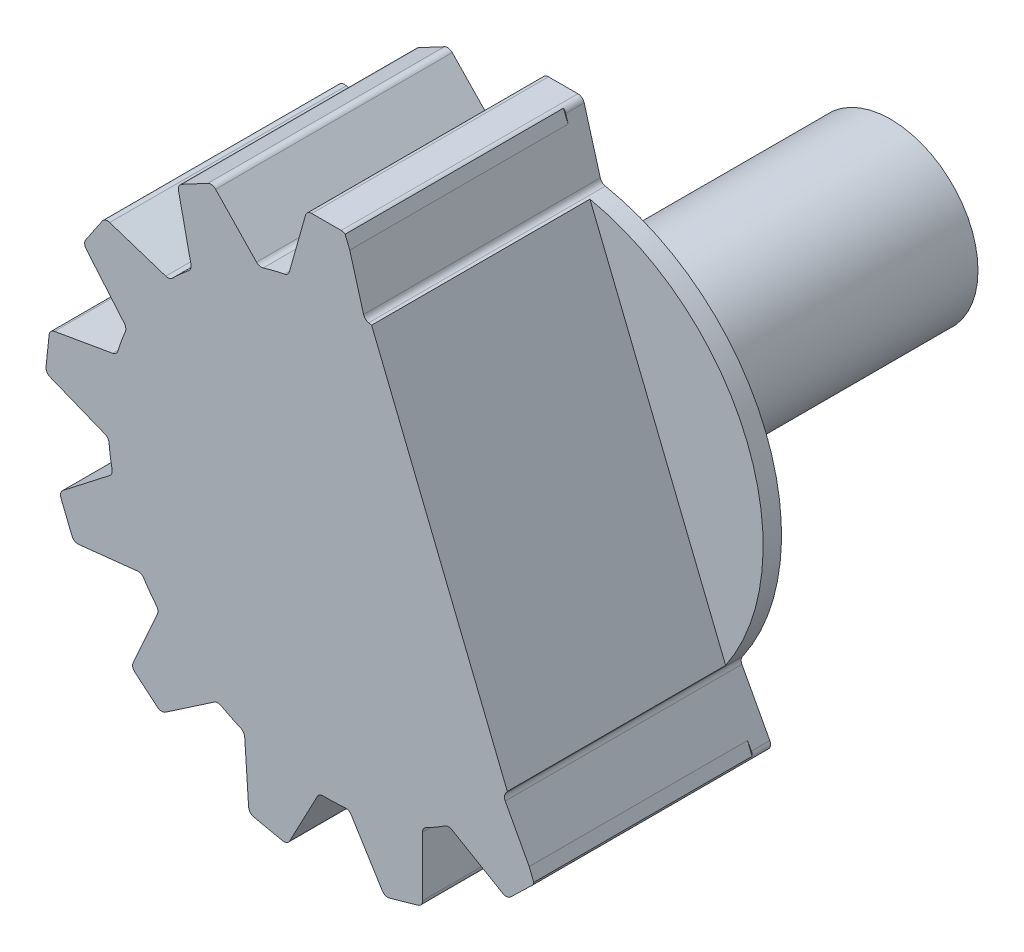
SolidWorks part; units mm, degrees
ref_plane "Front Plane" through (0, 0, 0) normal (0, 0, 1) x (1, 0, 0)
ref_plane "Top Plane" through (0, 0, 0) normal (0, 1, 0) x (1, 0, 0)
ref_plane "Right Plane" through (0, 0, 0) normal (1, 0, 0) x (0, 0, -1)
sketch "Esquisse1" plane through (0, 0, 0) normal (0, 0, 1) x (1, 0, 0)
  circle A0 centre (0, 0) radius 10
  dimension "D1" = 20
extrude "Main Extrusion" add sketch "Esquisse1" along normal blind 10.8418
sketch "Esquisse2" plane through (0, 0, 10.8418) normal (0, 0, 1) x (1, 0, 0)
  line L0 (-1.75, 9.8457) -> (1.75, 9.8457)
  line L1 (1.75, 9.8457) -> (0.9, 12.8457)
  line L2 (0.9, 12.8457) -> (-0.9, 12.8457)
  line L3 (-0.9, 12.8457) -> (-1.75, 9.8457)
  circle A0 centre (0, 0) radius 10 construction
  point P3 (0, 9.8457)
  dimension "D1" = 3.5
  dimension "D2" = 1.8
  dimension "D3" = 3
extrude "Gear Element" add sketch "Esquisse2" against normal up to surface (10.8418 mm away) up to face at (10, 0, 0)
ref_axis "Axe1" through (0, 0, -16) along (0, 0, 1)
fillet "Congé1" radius 0.3 4 edges at (0.9, 12.8457, 5.4209) (-0.9, 12.8457, 5.4209) (-1.75, 9.8457, 5.4209) (1.75, 9.8457, 5.4209)
pattern_circular "Répétition circulaire1" count 9 every 28 about axis through (0, 0, -16) along (0, 0, 1) of "Gear Element", "Congé1"
sketch "Esquisse3" plane through (0, 0, 0) normal (0, 0, -1) x (-1, 0, 0)
  circle A0 centre (0, 0) radius 4
  dimension "D1" = 8
extrude "Main Axe" add sketch "Esquisse3" along normal blind 15
sketch "Esquisse4" plane through (0, 0, -15) normal (0, 0, -1) x (-1, 0, 0)
  line L1 (-2.5, 0.5) -> (2.5, 0.5)
  line L2 (-2.5, 0.5) -> (-2.5, -0.5)
  line L3 (-2.5, -0.5) -> (2.5, -0.5)
  line L4 (2.5, 0.5) -> (2.5, -0.5)
  point P4 (-2.5, 0)
  point P7 (0, 0.5)
  dimension "D1" = 1
  dimension "D2" = 5
extrude "Axe Trait" cut sketch "Esquisse4" against normal blind 3
sketch "Esquisse5" plane through (0, 0, 10.8418) normal (0, 0, 1) x (1, 0, 0)
  line L0 (0.8541, 12.785) -> (9.4956, -8.6034)
  line L1 (9.4956, -8.6034) -> (13.5926, -6.9481)
  line L2 (13.5926, -6.9481) -> (4.9511, 14.4403)
  line L3 (4.9511, 14.4403) -> (0.8541, 12.785)
  arc A1 (8.2043, -5.7174) -> (1.9301, 9.812) centre (0, 0) ccw construction
  arc A2 (9.4076, -8.7728) -> (9.4637, -8.4153) centre (9.1992, -8.557) ccw construction
  arc A3 (0.9618, 12.6275) -> (0.6732, 12.8457) centre (0.6732, 12.5457) ccw construction
  point P3 (11.5762, -5.6039)
  point P12 (0.935, 12.8272)
extrude "Enlèv. mat.-Extru.1" cut sketch "Esquisse5" against normal blind 10
